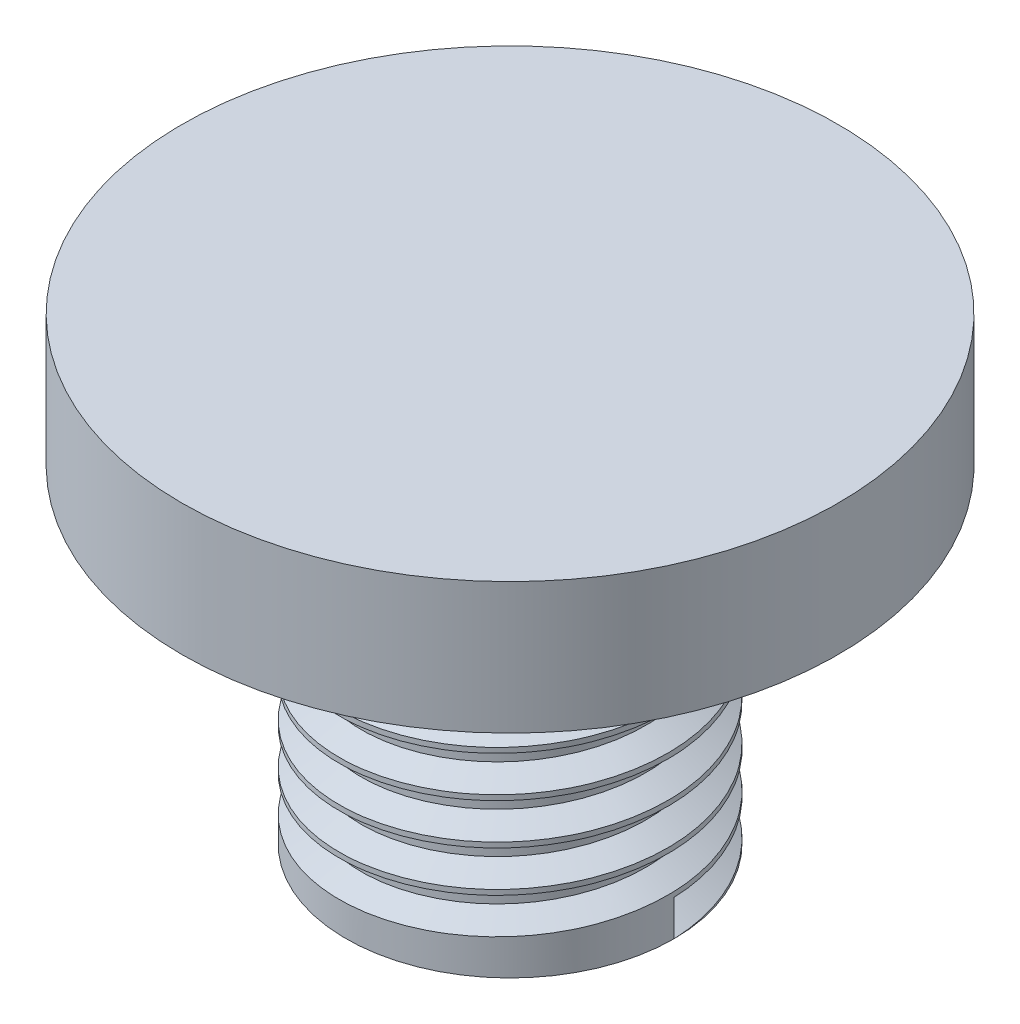
SolidWorks part; units mm, degrees
ref_plane "Front Plane" through (0, 0, 0) normal (0, 0, 1) x (1, 0, 0)
ref_plane "Top Plane" through (0, 0, 0) normal (0, 1, 0) x (1, 0, 0)
ref_plane "Right Plane" through (0, 0, 0) normal (1, 0, 0) x (0, 0, -1)
sketch "Sketch1" plane through (0, 0, 0) normal (0, 1, 0) x (1, 0, 0)
  circle A0 centre (0, 0) radius 1
  dimension "D1" = 2
extrude "Boss-Extrude1" add sketch "Sketch1" along normal blind 2
sketch "Sketch2" plane through (0, 2, 0) normal (0, 1, 0) x (1, 0, 0)
  circle A0 centre (0, 0) radius 2
  dimension "D1" = 4
extrude "Boss-Extrude2" add sketch "Sketch2" along normal blind 0.8
thread "Thread1" pitch 0.25 method cut profile "Thread Profile1" start angle 0, offset 0, length 0, pitch 0.25, diameter 2
ref_plane "Plane1" through (1, 0, 0) normal (0, 0, 1) x (1, 0, 0)
sketch "Thread Profile1" plane through (1, 0, 0) normal (0, 0, 1) x (1, 0, 0)
  line L0 (0, 0) -> (0, 0.25) construction
  line L11 (0, 0) -> (0, 0.2187)
  line L12 (0, 0.2187) -> (-0.1353, 0.1406)
  line L13 (-0.1353, 0.1406) -> (-0.1353, 0.0781)
  line L15 (-0.1353, 0.0781) -> (0, 0)
  line L17 (-0.1353, 0.1094) -> (0, 0.1094) construction
  point P2 (0, 0)
  dimension "Pitch" = 0.25
  dimension "Profile_Angle" = 60
  dimension "Profile_Land" = 0.0625
  dimension "Profile_Height" = 0.1353
